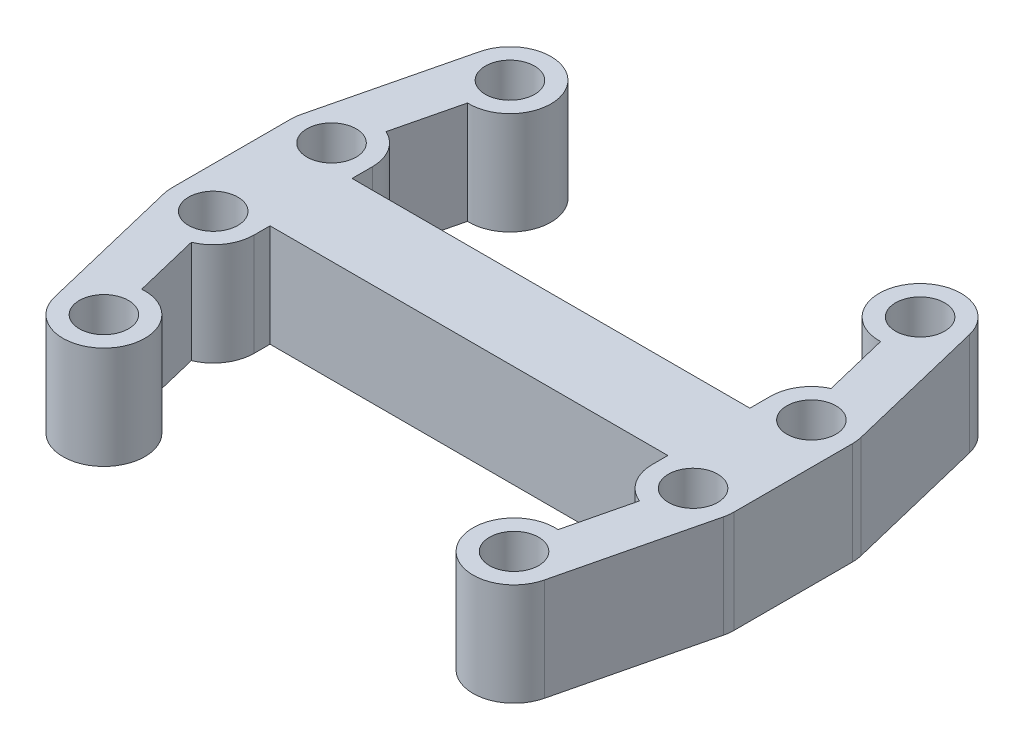
SolidWorks part; units mm, degrees
ref_plane "Front Plane" through (0, 0, 0) normal (0, 0, 1) x (1, 0, 0)
ref_plane "Top Plane" through (0, 0, 0) normal (0, 1, 0) x (1, 0, 0)
ref_plane "Right Plane" through (0, 0, 0) normal (1, 0, 0) x (0, 0, -1)
sketch "Sketch2" plane through (0, 0, 0) normal (0, 1, 0) x (1, 0, 0)
  line L1 (-17.2225, 7.6356) -> (-15.9921, 12.7022)
  line L2 (-18.9603, 16.6243) -> (-21.6591, 5.5118)
  line L3 (-21.7487, 4.7625) -> (-21.7488, -4.3974)
  line L8 (-17.3427, -7.324) -> (-16.1173, -12.3918)
  line L26 (-18.9611, -16.3038) -> (-21.6598, -5.1436)
  line L29 (0, 10.8515) -> (0, -11.8971) construction
  line L30 (17.2225, 7.6356) -> (15.9921, 12.7022)
  line L31 (18.9603, 16.6243) -> (21.6591, 5.5118)
  line L32 (21.7487, 4.7625) -> (21.7488, -4.3974)
  line L33 (18.9611, -16.3038) -> (21.6598, -5.1436)
  line L34 (17.3427, -7.324) -> (16.1173, -12.3918)
  line L35 (-15.3988, 4.7625) -> (-15.3988, 3.175)
  line L36 (-15.3988, 3.175) -> (15.3988, 3.175)
  line L37 (-15.3987, -4.3974) -> (-15.3988, -3.175)
  line L38 (-15.3988, -3.175) -> (15.3988, -3.175)
  line L39 (0, 3.175) -> (0, 0) construction
  line L40 (0, 0) -> (0, -3.175) construction
  line L41 (15.3987, -4.3974) -> (15.3988, -3.175)
  line L42 (15.3988, 4.7625) -> (15.3988, 3.175)
  circle A0 centre (-15.875, 15.875) radius 1.905
  arc A1 (-15.9921, 12.7022) -> (-18.9603, 16.6243) centre (-15.875, 15.875) ccw
  circle A2 centre (-18.5738, 4.7625) radius 1.905
  circle A5 centre (-18.5738, -4.3974) radius 1.905
  circle A8 centre (-15.875, -15.5575) radius 1.905
  arc A9 (-15.3988, 4.7625) -> (-17.2225, 7.6356) centre (-18.5738, 4.7625) ccw
  arc A10 (-15.3987, -4.3974) -> (-17.3427, -7.324) centre (-18.5738, -4.3974) cw
  arc A11 (-16.1173, -12.3918) -> (-18.9611, -16.3038) centre (-15.875, -15.5575) cw
  arc A16 (-21.6591, 5.5118) -> (-21.7487, 4.7625) centre (-18.5738, 4.7625) ccw
  arc A17 (-21.7488, -4.3974) -> (-21.6598, -5.1436) centre (-18.5738, -4.3974) ccw
  arc A18 (15.3988, 4.7625) -> (17.2225, 7.6356) centre (18.5738, 4.7625) cw
  arc A19 (15.9921, 12.7022) -> (18.9603, 16.6243) centre (15.875, 15.875) cw
  arc A20 (21.6591, 5.5118) -> (21.7487, 4.7625) centre (18.5738, 4.7625) cw
  arc A21 (21.7488, -4.3974) -> (21.6598, -5.1436) centre (18.5738, -4.3974) cw
  arc A22 (15.3987, -4.3974) -> (17.3427, -7.324) centre (18.5738, -4.3974) ccw
  arc A23 (16.1173, -12.3918) -> (18.9611, -16.3038) centre (15.875, -15.5575) ccw
  circle A24 centre (15.875, -15.5575) radius 1.905
  circle A25 centre (18.5738, -4.3974) radius 1.905
  circle A26 centre (18.5738, 4.7625) radius 1.905
  circle A27 centre (15.875, 15.875) radius 1.905
  point P37 (0, -4.3974)
  point P48 (-15.3987, -2.4862)
  dimension "D1" = 3.81
  dimension "D2" = 3.175
  dimension "D3" = 3.175
  dimension "D4" = 15.875
  dimension "D5" = 15.875
  dimension "D6" = 15.5575
  dimension "D7" = 4.7625
  dimension "D8" = 18.5738
  dimension "D9" = 4.3974
  dimension "D10" = 3.81
  dimension "D11" = 6.35
extrude "Boss-Extrude1" add sketch "Sketch2" along normal blind 7.9375
